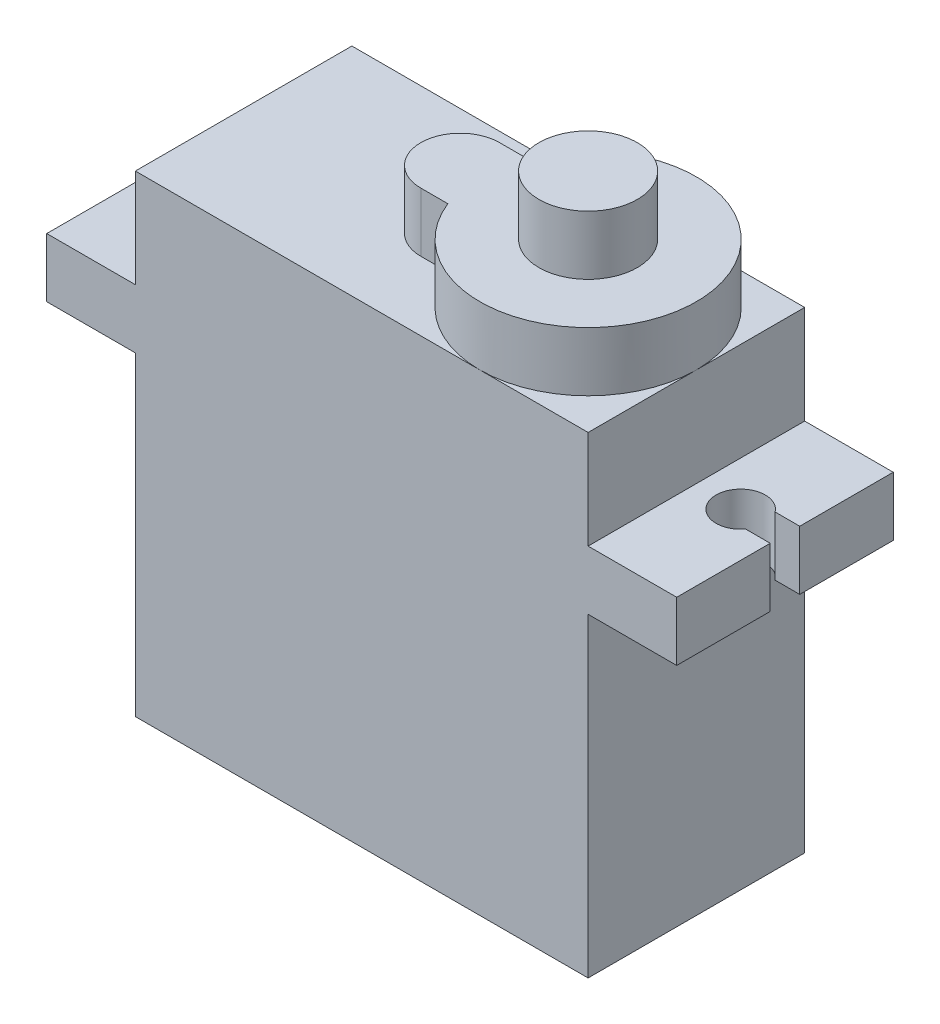
SolidWorks part; units mm, degrees
material "1060 Alloy"
ref_plane "Front Plane" through (0, 0, 0) normal (0, 0, 1) x (1, 0, 0)
ref_plane "Top Plane" through (0, 0, 0) normal (0, 1, 0) x (1, 0, 0)
ref_plane "Right Plane" through (0, 0, 0) normal (1, 0, 0) x (0, 0, -1)
sketch "Sketch1" plane through (0, 0, 0) normal (0, 1, 0) x (1, 0, 0)
  line L1 (-11.5, -5.5) -> (11.5, -5.5)
  line L2 (-11.5, -5.5) -> (-11.5, 5.5)
  line L3 (-11.5, 5.5) -> (11.5, 5.5)
  line L4 (11.5, -5.5) -> (11.5, 5.5)
  line L5 (-11.5, -5.5) -> (11.5, 5.5) construction
  line L6 (-11.5, 5.5) -> (11.5, -5.5) construction
  point P0 (0, 0)
  dimension "D1" = 11
  dimension "D2" = 23
extrude "Boss-Extrude1" add sketch "Sketch1" along normal blind 24
sketch "Sketch2" plane through (11.5, 0, 0) normal (1, 0, 0) x (0, 0, -1)
  line L0 (-5.5, 24) -> (-5.5, 0) construction
  line L1 (-5.5, 19) -> (5.5, 19)
  line L2 (-5.5, 19) -> (-5.5, 16)
  line L3 (-5.5, 16) -> (5.5, 16)
  line L4 (5.5, 19) -> (5.5, 16)
  line L5 (5.5, 24) -> (5.5, 0) construction
  line L7 (-5.5, 0) -> (5.5, 0) construction
  dimension "D1" = 16
  dimension "D2" = 3
extrude "Boss-Extrude2" add sketch "Sketch2" along normal blind 4.5 and the other way blind 27.5
sketch "Sketch3" plane through (0, 24, 0) normal (0, 1, 0) x (1, 0, 0)
  line L0 (11.5, -5.5) -> (11.5, 5.5) construction
  line L3 (-0.5, 2) -> (0.8765, 2)
  line L4 (-0.5, -2) -> (0.8765, -2)
  line L5 (-11.5, 5.5) -> (-11.5, -5.5) construction
  line L6 (11.5, -5.5) -> (11.5, 5.5) construction
  circle A0 centre (6, 0) radius 2.5
  arc A1 (0.8765, -2) -> (0.8765, 2) centre (6, 0) ccw
  arc A2 (-0.5, 2) -> (-0.5, -2) centre (-0.5, 0) ccw
  dimension "D1" = 5
  dimension "D3" = 2
  dimension "D2" = 11
  dimension "D4" = 5.5
extrude "Boss-Extrude3" add sketch "Sketch3" along normal blind 3
sketch "Sketch4" plane through (0, 27, 0) normal (0, 1, 0) x (1, 0, 0)
  circle A0 centre (6, 0) radius 2.5
extrude "Boss-Extrude4" add sketch "Sketch4" along normal blind 3 and the other way up to surface (3 mm away) other way up to face at (-1.666, 24, 0)
sketch "Sketch5" plane through (0, 19, 0) normal (0, 1, 0) x (1, 0, 0)
  line L0 (-16, -0.75) -> (-14.75, -0.75)
  line L1 (-16, 5.5) -> (-16, -5.5) construction
  line L3 (-14.75, 0.75) -> (-16, 0.75)
  line L4 (-16, 0.75) -> (-16, -0.75)
  line L5 (14.75, 0.75) -> (16, 0.75)
  line L6 (16, 5.5) -> (16, -5.5) construction
  line L7 (16, 0.75) -> (16, -0.75)
  line L8 (16, -0.75) -> (14.75, -0.75)
  arc A0 (-14.75, -0.75) -> (-14.75, 0.75) centre (-13.75, 0) ccw
  arc A1 (14.75, 0.75) -> (14.75, -0.75) centre (13.75, 0) ccw
  point P1 (-16, 0)
  dimension "D1" = 2.5
  dimension "D2" = 1.5
  dimension "D3" = 27.5
extrude "Cut-Extrude1" cut sketch "Sketch5" against normal blind 4
equation "\"D2@Sketch3\"=9+\"D3@Sketch3\""
